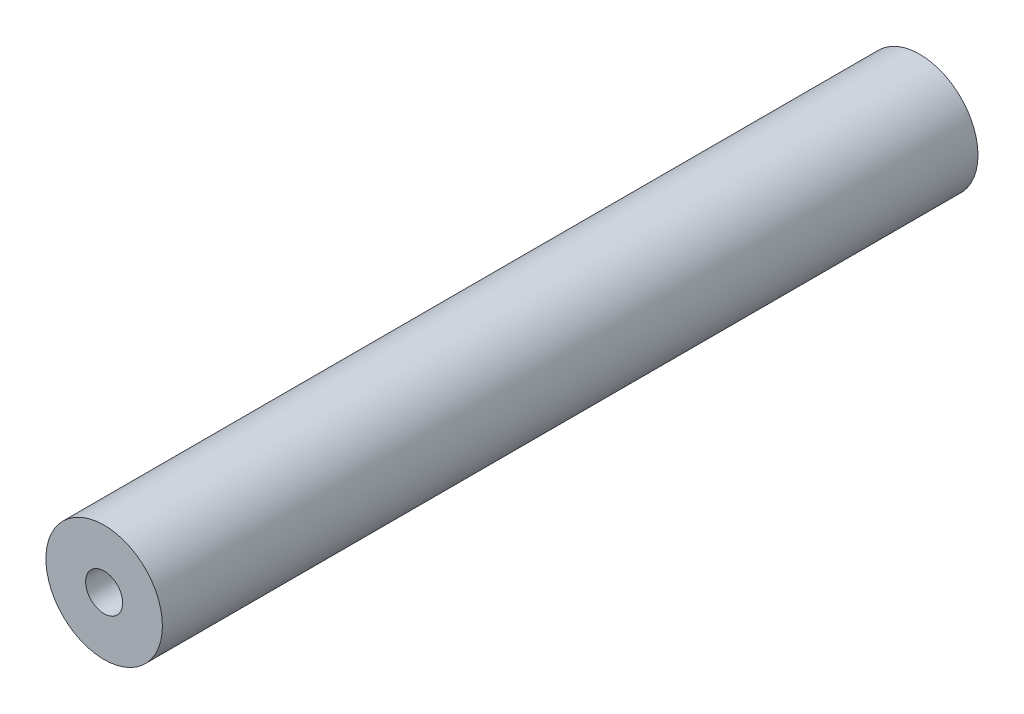
SolidWorks part; units mm, degrees
ref_plane "Front Plane" through (0, 0, 0) normal (0, 0, 1) x (1, 0, 0)
ref_plane "Top Plane" through (0, 0, 0) normal (0, 1, 0) x (1, 0, 0)
ref_plane "Right Plane" through (0, 0, 0) normal (1, 0, 0) x (0, 0, -1)
sketch "Sketch1" plane through (0, 0, 0) normal (0, 0, 1) x (1, 0, 0)
  circle A1 centre (0, 0) radius 6.35
  circle A2 centre (0, 0) radius 2.0193
  dimension "D2" = 12.7
  dimension "D3" = 4.0386
extrude "Boss-Extrude1" add sketch "Sketch1" along normal mid plane 88.9 contours A1 A2 region at (-6.1704, 0, 0)
